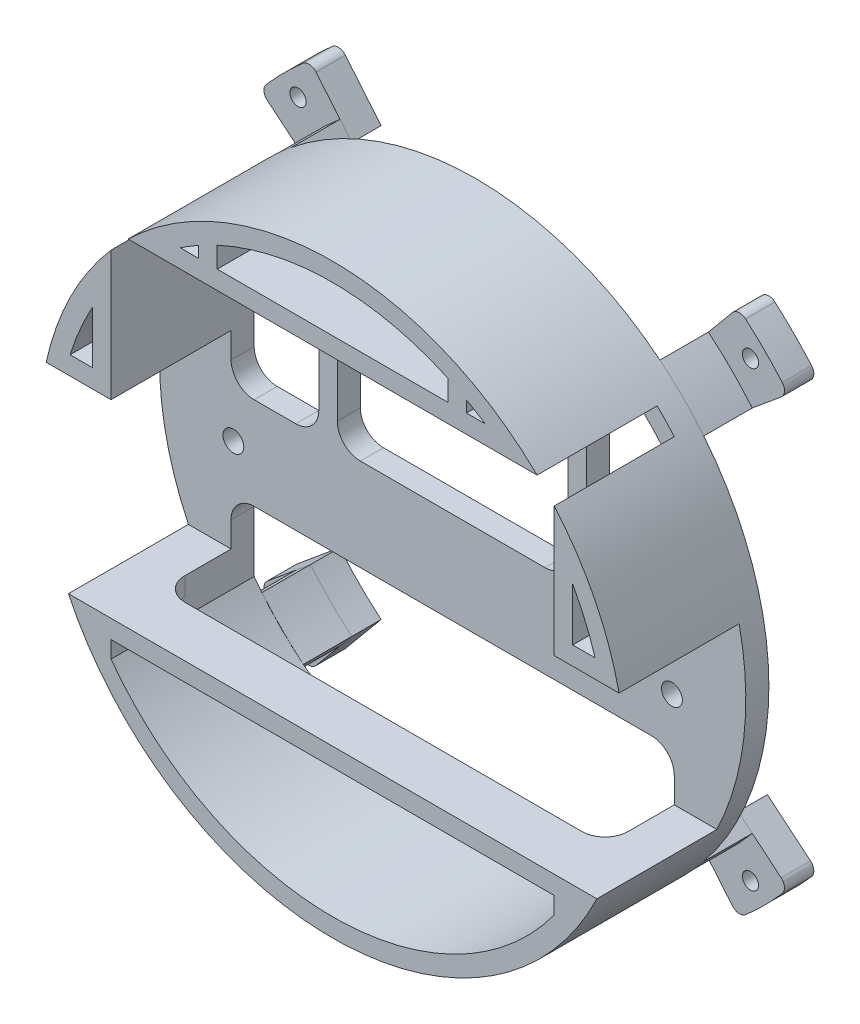
SolidWorks part; units mm, degrees
ref_plane "Front Plane" through (0, 0, 0) normal (0, 0, 1) x (1, 0, 0)
ref_plane "Top Plane" through (0, 0, 0) normal (0, 1, 0) x (1, 0, 0)
ref_plane "Right Plane" through (0, 0, 0) normal (1, 0, 0) x (0, 0, -1)
sketch "Sketch1" plane through (0, 0, 0) normal (0, 0, 1) x (1, 0, 0)
  line L0 (0, -63.5) -> (0, 63.5) construction
  line L1 (-47.5, -7) -> (47.5, -7) construction
  line L2 (-47.5, 7.5) -> (47.5, 7.5)
  line L3 (-47.5, -21.5) -> (47.5, -21.5)
  line L4 (-57.2364, -27.5) -> (57.2364, -27.5)
  line L5 (-48, 17.5) -> (48, 17.5)
  line L6 (-48, 17.5) -> (-48, 45.5)
  line L7 (-48, 45.5) -> (48, 45.5)
  line L8 (48, 17.5) -> (48, 45.5)
  line L9 (-48, 17.5) -> (48, 45.5) construction
  line L10 (-48, 45.5) -> (48, 17.5) construction
  line L11 (-48, 17.5) -> (-56.8683, 17.5)
  line L12 (-52, 17.5) -> (-52, 28.918)
  line L13 (-62.0484, 13.5) -> (62.0484, 13.5)
  line L14 (48, 17.5) -> (56.8683, 17.5)
  line L15 (52, 17.5) -> (52, 28.918)
  line L16 (-33.0151, 49.5) -> (33.0151, 49.5)
  line L17 (-50.4777, -31.5) -> (50.4777, -31.5)
  line L18 (48, 17.5) -> (48, -31.5) construction
  line L19 (48, -31.5) -> (48, -35.1603)
  line L20 (-48, 17.5) -> (-48, -31.5) construction
  line L21 (-48, -31.5) -> (-48, -35.1603)
  circle A0 centre (0, 0) radius 63.5
  arc A2 (-47.5, 7.5) -> (-47.5, -21.5) centre (-47.5, -7) ccw
  arc A3 (47.5, -21.5) -> (47.5, 7.5) centre (47.5, -7) ccw
  circle A4 centre (0, 0) radius 59.5
  point P7 (0, 0)
  point P9 (0, -7)
  point P15 (0, 31.5)
  dimension "D1" = 127
  dimension "D2" = 18
  dimension "D10" = 119
  dimension "D3" = 95
  dimension "D4" = 29
  dimension "D5" = 96
  dimension "D6" = 28
  dimension "D7" = 6
  dimension "D8" = 7
  dimension "D9" = 6
  dimension "D11" = 4
  dimension "D12" = 4
  dimension "D13" = 4
  dimension "D14" = 4
extrude "Boss-Extrude1" add sketch "Sketch1" along normal blind 31 contours A4 L4 A0 | L4 A4 L17 | L13 A4 L14 L5 L11 | L6 A4 L12 L11 | A4 L6 A0 L13 | A4 L13 A0 L8 | L15 A4 L8 L14 | A4 L7 A0 | L7 A4 L16 | L19 A4 L17 | L17 A4 L21
sketch "Sketch2" plane through (0, 0, 0) normal (0, 0, -1) x (-1, 0, 0)
  line L0 (44.2945, 45.5) -> (-44.2945, 45.5) construction
  line L1 (-48, 45.5) -> (-25, 45.5)
  line L2 (-48, 45.5) -> (-48, 17.5)
  line L3 (-48, 17.5) -> (-25, 17.5)
  line L4 (-25, 45.5) -> (-25, 17.5)
  line L5 (48, 17.5) -> (-48, 17.5) construction
  line L6 (48, 17.5) -> (48, 41.5722) construction
  line L7 (25, 45.5) -> (48, 45.5)
  line L8 (25, 45.5) -> (25, 17.5)
  line L9 (25, 17.5) -> (48, 17.5)
  line L10 (48, 45.5) -> (48, 17.5)
  line L11 (-48, 17.5) -> (-48, 41.5722) construction
  arc A0 (48, 41.5722) -> (-48, 41.5722) centre (0, 0) ccw
  line M12 (48, 41.5722) -> (48, 17.5)
  line M13 (48, 17.5) -> (-48, 17.5)
  line M14 (-48, 17.5) -> (-48, 41.5722)
  dimension "D1" = 25
  dimension "D2" = 25
extrude "Boss-Extrude3" add sketch "Sketch2" against normal blind 10 contours A0 L7 L8 M12 M13 | L1 A0 L4 M14 M13
sketch "Sketch4" plane through (0, 0, 0) normal (0, 0, -1) x (-1, 0, 0)
  line L0 (57.2364, -27.5) -> (-57.2364, -27.5) construction
  line L1 (-57.2364, -27.5) -> (57.2364, -27.5)
  line L2 (62.0484, 13.5) -> (-62.0484, 13.5)
  arc A0 (57.2364, -27.5) -> (62.0484, 13.5) centre (0, 0) ccw
  arc A1 (62.0484, 13.5) -> (-62.0484, 13.5) centre (0, 0) ccw construction
  arc A2 (-62.0484, 13.5) -> (-57.2364, -27.5) centre (0, 0) ccw
extrude "Boss-Extrude4" add sketch "Sketch4" against normal blind 5
sketch "Sketch6" plane through (0, 0, 5) normal (0, 0, 1) x (1, 0, 0)
  line L0 (0, 13.5) -> (0, -27.5) construction
  line L1 (-62.0484, 13.5) -> (62.0484, 13.5) construction
  line L2 (57.2364, -27.5) -> (-57.2364, -27.5) construction
  line L3 (-47.5, -7) -> (47.5, -7) construction
  line L4 (-48, 17.5) -> (-48, 13.5) construction
  line L5 (-48, 13.5) -> (-48, 3)
  line L6 (48, 17.5) -> (48, 13.5) construction
  line L7 (-62.0484, 13.5) -> (62.0484, 13.5) construction
  line L8 (48, 13.5) -> (48, 3)
  line L9 (48, 3) -> (-48, 3)
  line L10 (-48, 13.5) -> (48, 13.5)
  line L11 (-48, 3) -> (-48, -17)
  line L12 (-48, -17) -> (48, -17)
  line L13 (48, -17) -> (48, 3)
  line L14 (-48, -17) -> (-48, -27.5)
  line L15 (-57.2364, -27.5) -> (57.2364, -27.5) construction
  line L16 (48, -17) -> (48, -27.5)
  line L17 (-48, -27.5) -> (48, -27.5)
  line L18 (25, 17.5) -> (25, 13.5) construction
  line L19 (-25, 17.5) -> (-25, 13.5) construction
  line L20 (25, 13.5) -> (29, 13.5)
  line L21 (25, 13.5) -> (25, 3)
  line L22 (25, 3) -> (29, 3)
  line L23 (29, 13.5) -> (29, 3)
  line L25 (-25, 13.5) -> (-29, 13.5)
  line L26 (-25, 13.5) -> (-25, 3)
  line L27 (-25, 3) -> (-29, 3)
  line L28 (-29, 13.5) -> (-29, 3)
  circle A0 centre (-47.5, -7) radius 2.25
  circle A1 centre (47.5, -7) radius 2.25
  point P9 (0, -7)
  line M9 (-57.2364, -27.5) -> (57.2364, -27.5)
  line M11 (62.0484, 13.5) -> (-62.0484, 13.5)
  dimension "D1" = 4.5
  dimension "D2" = 4.5
  dimension "D3" = 95
  dimension "D4" = 10
  dimension "D5" = 10
  dimension "D6" = 4
  dimension "D7" = 4
extrude "Cut-Extrude1" cut sketch "Sketch6" against normal through all contours L9 L8 L5 M11 | L16 L12 L14 M9 | L13 A1 | L13 A1 | L11 A0 | L11 A0 | L23 L9 L8 M11 | L28 L5 L9 M11
sketch "Sketch7" plane through (0, 0, 0) normal (0, 0, -1) x (-1, 0, 0)
  line L6 (-29, 17.5) -> (-48, 17.5)
  line L7 (-29, 45.5) -> (-38.3406, 45.5)
  line L8 (-48, 17.5) -> (-48, 35.1603)
  line L9 (-52, 17.5) -> (-52, 28.918) construction
  line L10 (-29, 17.5) -> (-29, 45.5)
  line L11 (-25, 45.5) -> (-25, 17.5) construction
  line L12 (29, 17.5) -> (48, 17.5)
  line L13 (29, 45.5) -> (38.3406, 45.5)
  line L14 (48, 17.5) -> (48, 35.1603)
  line L15 (29, 17.5) -> (29, 45.5)
  line L16 (25, 45.5) -> (25, 17.5) construction
  line L17 (52, 17.5) -> (52, 28.918) construction
  circle A3 centre (0, 0) radius 63.5 construction
  arc A4 (-38.3406, 45.5) -> (-48, 35.1603) centre (0, 0) ccw
  arc A6 (48, 35.1603) -> (38.3406, 45.5) centre (0, 0) ccw
  dimension "D3" = 4
  dimension "D6" = 4
  dimension "D1" = 4
  dimension "D2" = 4
  dimension "D4" = 4
  dimension "D5" = 4
extrude "Cut-Extrude2" cut sketch "Sketch7" against normal blind 10
sketch "Sketch9" plane through (0, 0, 0) normal (0, 0, -1) x (-1, 0, 0)
  line L0 (-48, 13.5) -> (-29, 13.5) construction
  line L1 (-48, -27.5) -> (48, -27.5)
  line L2 (-48, -27.5) -> (-48, -31.5)
  line L3 (-48, -31.5) -> (48, -31.5)
  line L4 (48, -27.5) -> (48, -31.5)
  line L5 (-48, 17.5) -> (-29, 17.5)
  line L6 (-48, 17.5) -> (-48, 13.5)
  line L7 (-48, 13.5) -> (-29, 13.5)
  line L8 (-29, 17.5) -> (-29, 13.5)
  line L9 (25, 45.5) -> (25, 17.5) construction
  line L10 (-25, 17.5) -> (25, 17.5)
  line L11 (-25, 17.5) -> (-25, 13.5)
  line L12 (-25, 13.5) -> (25, 13.5)
  line L13 (25, 17.5) -> (25, 13.5)
  line L14 (29, 17.5) -> (48, 17.5)
  line L15 (29, 17.5) -> (29, 13.5)
  line L16 (29, 13.5) -> (48, 13.5)
  line L17 (48, 17.5) -> (48, 13.5)
  line L18 (-29, 17.5) -> (-29, 45.5) construction
  line L19 (33.0151, 49.5) -> (-33.0151, 49.5) construction
  line L20 (-25, 45.5) -> (25, 45.5)
  line L21 (-25, 45.5) -> (-25, 49.5)
  line L22 (-25, 49.5) -> (25, 49.5)
  line L23 (25, 45.5) -> (25, 49.5)
  line L24 (25, 45.5) -> (25, 17.5) construction
extrude "Cut-Extrude4" cut sketch "Sketch9" against normal blind 20
sketch "Sketch10" plane through (0, 0, 0) normal (0, 0, -1) x (-1, 0, 0)
  line L0 (-29.0076, 49.5) -> (-29.0076, 51.9501)
  line L1 (-25, 49.5) -> (-33.0151, 49.5) construction
  line L2 (-25, 49.5) -> (-25, 53.9931)
  line L3 (-29.0076, 49.5) -> (-25, 49.5)
  line L4 (25, 49.5) -> (25, 53.9931)
  line L5 (29.0076, 49.5) -> (29.0076, 51.9501)
  line L6 (33.0151, 49.5) -> (25, 49.5) construction
  line L7 (29.0076, 49.5) -> (25, 49.5)
  arc A0 (33.0151, 49.5) -> (-33.0151, 49.5) centre (0, 0) ccw construction
  arc A1 (-29.0076, 51.9501) -> (-25, 53.9931) centre (0, 0) cw
  arc A2 (29.0076, 51.9501) -> (25, 53.9931) centre (0, 0) ccw
  line M21 (-25, 49.5) -> (-33.0151, 49.5)
  arc M22 (-33.0151, 49.5) -> (33.0151, 49.5) centre (0, 0) cw
  line M23 (33.0151, 49.5) -> (25, 49.5)
extrude "Boss-Extrude5" add sketch "Sketch10" against normal up to surface (31 mm away) contours L2 L0 M21 M22 | L5 L4 M23 M22
fillet "Fillet3" radius 5 18 edges at (25, 47.5, 20) (48, 15.5, 20) (-29, 15.5, 20) (25, 15.5, 20) (-29, 3, 2.5) (25, 3, 2.5) (48, 3, 2.5) (48, -29.5, 20) (48, -17, 2.5) (-48, -17, 2.5) (-48, -29.5, 20) (29, 3, 2.5) (-25, 3, 2.5) (-48, 3, 2.5) (-25, 47.5, 20) (-48, 15.5, 20) (-25, 15.5, 20) (29, 15.5, 20)
sketch "Sketch11" plane through (0, 0, 31) normal (0, 0, 1) x (1, 0, 0)
  line L0 (-44.2945, 45.5) -> (44.2945, 45.5) construction
  line L1 (48, 3) -> (-48, 3)
  line L2 (48, 3) -> (48, 45.5)
  line L3 (48, 45.5) -> (-48, 45.5)
  line L4 (-48, 3) -> (-48, 45.5)
  line L5 (20, 3) -> (-20, 3) construction
extrude "Cut-Extrude5" cut sketch "Sketch11" against normal up to surface (26 mm away) up to face at (49.75, -7, 5)
sketch "Sketch12" plane through (0, 0, 0) normal (0, 0, -1) x (-1, 0, 0)
  line L0 (0, -78.7666) -> (0, 96.8427) construction
  line L1 (-63.4303, 63.4303) -> (64.9233, -64.9233)
  line L2 (46.3227, -37.3424) -> (49.3997, -39.8989)
  line L3 (-73.359, -73.359) -> (86.3029, 86.3029)
  line L4 (37.3424, -46.3227) -> (39.8989, -49.3997)
  line L5 (-46.3227, -37.3424) -> (-49.3997, -39.8989)
  line L6 (-37.3424, -46.3227) -> (-39.8989, -49.3997)
  line L7 (-37.3424, 46.3227) -> (-39.8989, 49.3997)
  line L8 (-46.3227, 37.3424) -> (-49.3997, 39.8989)
  line L9 (46.3227, 37.3424) -> (49.3997, 39.8989)
  line L10 (37.3424, 46.3227) -> (39.8989, 49.3997)
  arc A0 (-48, -35.1603) -> (48, -35.1603) centre (0, 0) ccw construction
  circle A1 centre (0, 0) radius 63.5 construction
  arc A2 (49.3997, -39.8989) -> (39.8989, -49.3997) centre (-6.7593, 6.7593) cw
  arc A3 (46.3227, -37.3424) -> (37.3424, -46.3227) centre (-6.7593, 6.7593) cw
  arc A4 (-37.3424, -46.3227) -> (-46.3227, -37.3424) centre (6.7593, 6.7593) cw
  arc A5 (-39.8989, -49.3997) -> (-49.3997, -39.8989) centre (6.7593, 6.7593) cw
  arc A6 (-46.3227, 37.3424) -> (-37.3424, 46.3227) centre (6.7593, -6.7593) cw
  arc A7 (-49.3997, 39.8989) -> (-39.8989, 49.3997) centre (6.7593, -6.7593) cw
  arc A8 (37.3424, 46.3227) -> (46.3227, 37.3424) centre (-6.7593, -6.7593) cw
  arc A9 (39.8989, 49.3997) -> (49.3997, 39.8989) centre (-6.7593, -6.7593) cw
  dimension "D3" = 6.35
  dimension "D4" = 4
extrude "Boss-Extrude6" add sketch "Sketch12" along normal blind 10.5 contours A3 L4 A2 L2 | A4 L5 A5 L6 | A6 L7 A7 L8 | A8 L9 A9 L10
sketch "Sketch14" plane through (0, 0, -10.5) normal (0, 0, -1) x (-1, 0, 0)
  line L0 (46.3227, -37.3424) -> (49.3997, -39.8989)
  line L1 (37.3424, -46.3227) -> (39.8989, -49.3997)
  line L2 (49.3997, -39.8989) -> (57.2145, -46.3916)
  line L3 (39.8989, -49.3997) -> (46.3916, -57.2145)
  line L4 (42.0396, -42.0396) -> (51.3899, -51.3899)
  line L5 (-49.3997, -39.8989) -> (-57.2145, -46.3916)
  line L6 (-46.3227, -37.3424) -> (-49.3997, -39.8989)
  line L7 (-42.0396, -42.0396) -> (-51.3899, -51.3899)
  line L8 (-37.3424, -46.3227) -> (-39.8989, -49.3997)
  line L9 (-39.8989, -49.3997) -> (-46.3916, -57.2145)
  line L10 (-39.8989, 49.3997) -> (-46.3916, 57.2145)
  line L11 (-37.3424, 46.3227) -> (-39.8989, 49.3997)
  line L12 (-42.0396, 42.0396) -> (-51.3899, 51.3899)
  line L13 (-46.3227, 37.3424) -> (-49.3997, 39.8989)
  line L14 (-49.3997, 39.8989) -> (-57.2145, 46.3916)
  line L15 (49.3997, 39.8989) -> (57.2145, 46.3916)
  line L16 (46.3227, 37.3424) -> (49.3997, 39.8989)
  line L17 (42.0396, 42.0396) -> (51.3899, 51.3899)
  line L18 (37.3424, 46.3227) -> (39.8989, 49.3997)
  line L19 (39.8989, 49.3997) -> (46.3916, 57.2145)
  arc A0 (46.3227, -37.3424) -> (37.3424, -46.3227) centre (-6.7593, 6.7593) cw
  circle A1 centre (48.9992, -48.9992) radius 1.75
  arc A2 (49.3997, -39.8989) -> (39.8989, -49.3997) centre (-6.7593, 6.7593) cw
  arc A3 (57.2145, -46.3916) -> (46.3916, -57.2145) centre (-6.7593, 6.7593) cw
  circle A4 centre (-48.9992, -48.9992) radius 1.75
  arc A5 (-46.3916, -57.2145) -> (-57.2145, -46.3916) centre (6.7593, 6.7593) cw
  arc A6 (-37.3424, -46.3227) -> (-46.3227, -37.3424) centre (6.7593, 6.7593) cw
  arc A7 (-39.8989, -49.3997) -> (-49.3997, -39.8989) centre (6.7593, 6.7593) cw
  circle A8 centre (-48.9992, 48.9992) radius 1.75
  arc A9 (-57.2145, 46.3916) -> (-46.3916, 57.2145) centre (6.7593, -6.7593) cw
  arc A10 (-46.3227, 37.3424) -> (-37.3424, 46.3227) centre (6.7593, -6.7593) cw
  arc A11 (-49.3997, 39.8989) -> (-39.8989, 49.3997) centre (6.7593, -6.7593) cw
  circle A12 centre (48.9992, 48.9992) radius 1.75
  arc A13 (46.3916, 57.2145) -> (57.2145, 46.3916) centre (-6.7593, -6.7593) cw
  arc A14 (37.3424, 46.3227) -> (46.3227, 37.3424) centre (-6.7593, -6.7593) cw
  arc A15 (39.8989, 49.3997) -> (49.3997, 39.8989) centre (-6.7593, -6.7593) cw
  point P16 (44.8683, -44.8683)
  dimension "D3" = 3.5
  dimension "D1" = 5.842
  dimension "D2" = 10.16
  dimension "D4" = 4
extrude "Boss-Extrude7" add sketch "Sketch14" along normal blind 6.35 separate body
fillet "Fillet4" radius 2 2 edges at (57.2145, 46.3916, -13.675) (46.3916, 57.2145, -13.675)
fillet "Fillet7" radius 2 2 edges at (46.3916, -57.2145, -13.675) (57.2145, -46.3916, -13.675)
fillet "Fillet8" radius 2 2 edges at (-57.2145, -46.3916, -13.675) (-46.3916, -57.2145, -13.675)
fillet "Fillet9" radius 2 2 edges at (-46.3916, 57.2145, -13.675) (-57.2145, 46.3916, -13.675)
